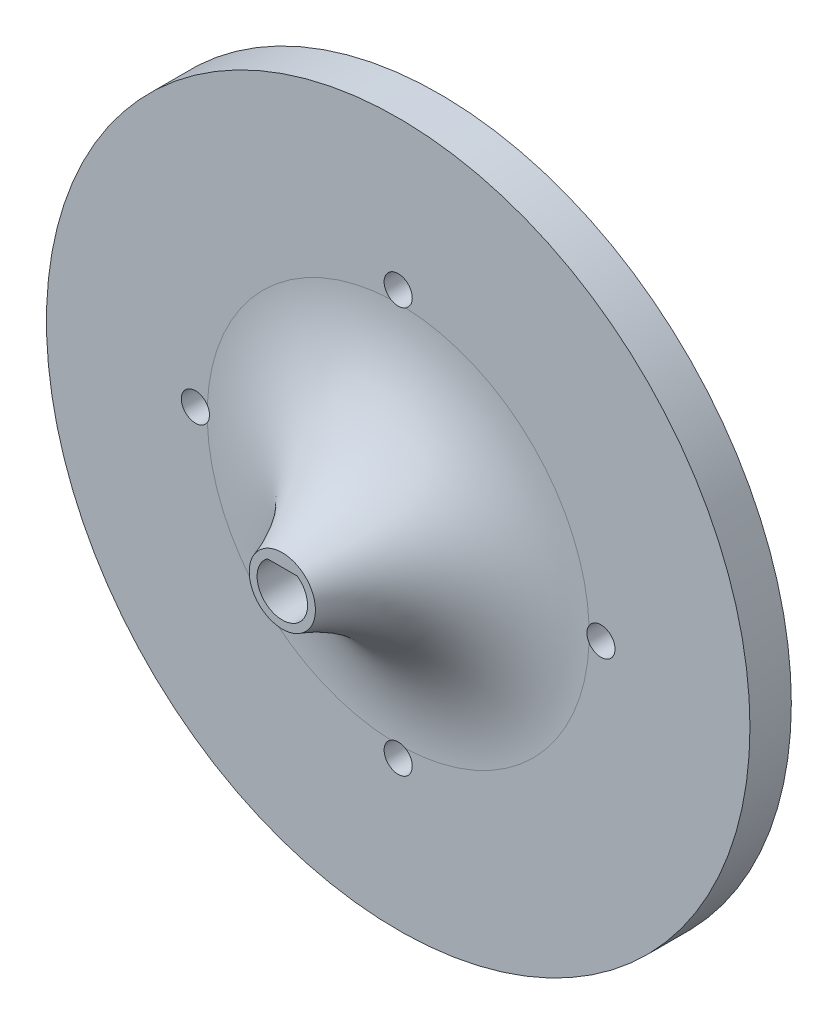
SolidWorks part; units mm, degrees
ref_plane "Front Plane" through (0, 0, 0) normal (0, 0, 1) x (1, 0, 0)
ref_plane "Top Plane" through (0, 0, 0) normal (0, 1, 0) x (1, 0, 0)
ref_plane "Right Plane" through (0, 0, 0) normal (1, 0, 0) x (0, 0, -1)
sketch "Sketch4" plane through (0, 0, 0) normal (0, 0, 1) x (1, 0, 0)
  line L0 (0, 0) -> (17, 0) construction
  line L1 (0, 0) -> (-17, 0) construction
  line L2 (-17, 0) -> (-17, 34)
  line L3 (-17, 34) -> (17, 34)
  line L4 (17, 34) -> (17, 0)
  arc A0 (17, 0) -> (-17, 0) centre (0, 0) cw
  dimension "D1" = 17
  dimension "D2" = 17
  dimension "D3" = 34
extrude "Boss-Extrude2" add sketch "Sketch4" along normal blind 5
sketch "Sketch5" plane through (0, 0, 5) normal (0, 0, 1) x (1, 0, 0)
  line L0 (-17, 0) -> (17, 0) construction
  circle A0 centre (0, -8.5) radius 4
  dimension "D1" = 8.5
extrude "Boss-Extrude3" add sketch "Sketch5" along normal blind 7
sketch "Sketch6" plane through (0, 0, 0) normal (0, 0, -1) x (-1, 0, 0)
  line L0 (-17, 0) -> (17, 0) construction
  arc A0 (-17, 0) -> (17, 0) centre (0, 0) ccw construction
  circle A1 centre (0, 17.7159) radius 15.5
extrude "Cut-Extrude1" cut sketch "Sketch6" against normal blind 4
sketch "Sketch7" plane through (0, 0, 4) normal (0, 0, -1) x (-1, 0, 0)
  line L0 (-15.5, 17.7159) -> (0, 17.7159) construction
  circle A0 centre (0, 17.7159) radius 15.5 construction
  circle A1 centre (0, 17.7159) radius 1.8
extrude "Cut-Extrude2" cut sketch "Sketch7" against normal blind 4
sketch "Sketch8" plane through (0, 0, 12) normal (0, 0, 1) x (1, 0, 0)
  line L0 (-1.4059, -7.12) -> (1.4059, -7.12)
  arc A1 (-1.4059, -7.12) -> (1.4059, -7.12) centre (0, -8.5) ccw
  point P8 (-1.4059, -7.12)
  point P9 (1.4059, -7.12)
extrude "Cut-Extrude3" cut sketch "Sketch8" against normal blind 6
sketch "Sketch10" plane through (0, 0, 12) normal (0, 0, 1) x (1, 0, 0)
  line L4 (1.4391, -7.04) -> (-1.4391, -7.04)
  arc A3 (-1.4391, -7.04) -> (1.4391, -7.04) centre (0, -8.5) ccw
extrude "Cut-Extrude4" cut sketch "Sketch10" against normal blind 7
sketch "Sketch11" plane through (0, 0, 12) normal (0, 0, 1) x (1, 0, 0)
  line L0 (1.4391, -7.04) -> (-1.4391, -7.04) construction
  line L1 (1.4391, -7.04) -> (-1.4391, -7.04)
  arc A0 (-1.4391, -7.04) -> (1.4391, -7.04) centre (0, -8.5) ccw construction
  circle A1 centre (0, -8.5) radius 4
  arc A3 (-1.4391, -7.04) -> (1.4391, -7.04) centre (0, -8.5) ccw
  circle A5 centre (0, -8.5) radius 4
  dimension "D1" = 0
extrude "Boss-Extrude4" add sketch "Sketch11" along normal blind 7
sketch "Sketch12" plane through (0, 0, 5) normal (0, 0, 1) x (1, 0, 0)
  circle A0 centre (0, -8.5) radius 42.5
extrude "Boss-Extrude5" add sketch "Sketch12" against normal blind 5
sketch "Sketch13" plane through (0, 0, 5) normal (0, 0, 1) x (1, 0, 0)
  circle A0 centre (0, -8.5) radius 42.5
  circle A1 centre (0, -8.5) radius 45.7739
extrude "Cut-Extrude5" cut sketch "Sketch13" against normal blind 5
sketch "Sketch14" plane through (0, 0, 0) normal (0, 0, -1) x (-1, 0, 0)
  line L0 (-42.5, -8.5) -> (42.5, -8.5) construction
  line L1 (0, 34) -> (0, -51) construction
  circle A0 centre (0, -8.5) radius 42.5 construction
  circle A1 centre (0, 16) radius 16
  circle A2 centre (0, -33) radius 16
  circle A3 centre (-24.5, -8.5) radius 16
  circle A4 centre (24.5, -8.5) radius 16
  dimension "D1" = 18
  dimension "D2" = 18
extrude "Cut-Extrude6" cut sketch "Sketch14" against normal blind 2.5
sketch "Sketch15" plane through (0, 0, 2.5) normal (0, 0, -1) x (-1, 0, 0)
  circle A0 centre (0, 16) radius 1.7
  circle A1 centre (-24.5, -8.5) radius 1.7
  circle A2 centre (24.5, -8.5) radius 1.7
  circle A3 centre (0, -33) radius 1.7
extrude "Cut-Extrude7" cut sketch "Sketch15" against normal blind 2.5
sketch "Sketch16" plane through (0, 0, 19) normal (0, 0, 1) x (1, 0, 0)
  line L0 (1.4391, -7.04) -> (-1.4391, -7.04) construction
  line L1 (1.4391, -7.04) -> (-1.4391, -7.04)
  line L2 (1.803, -6.04) -> (-1.803, -6.04)
  arc A0 (-1.4391, -7.04) -> (1.4391, -7.04) centre (0, -8.5) ccw construction
  arc A1 (-1.4391, -7.04) -> (1.4391, -7.04) centre (0, -8.5) ccw
  arc A2 (-1.803, -6.04) -> (1.803, -6.04) centre (0, -8.5) ccw
  dimension "D1" = 1
extrude "Cut-Extrude8" cut sketch "Sketch16" against normal blind 14
fillet "Fillet1" radius 20 1 edges at (-4, -8.5, 5)
